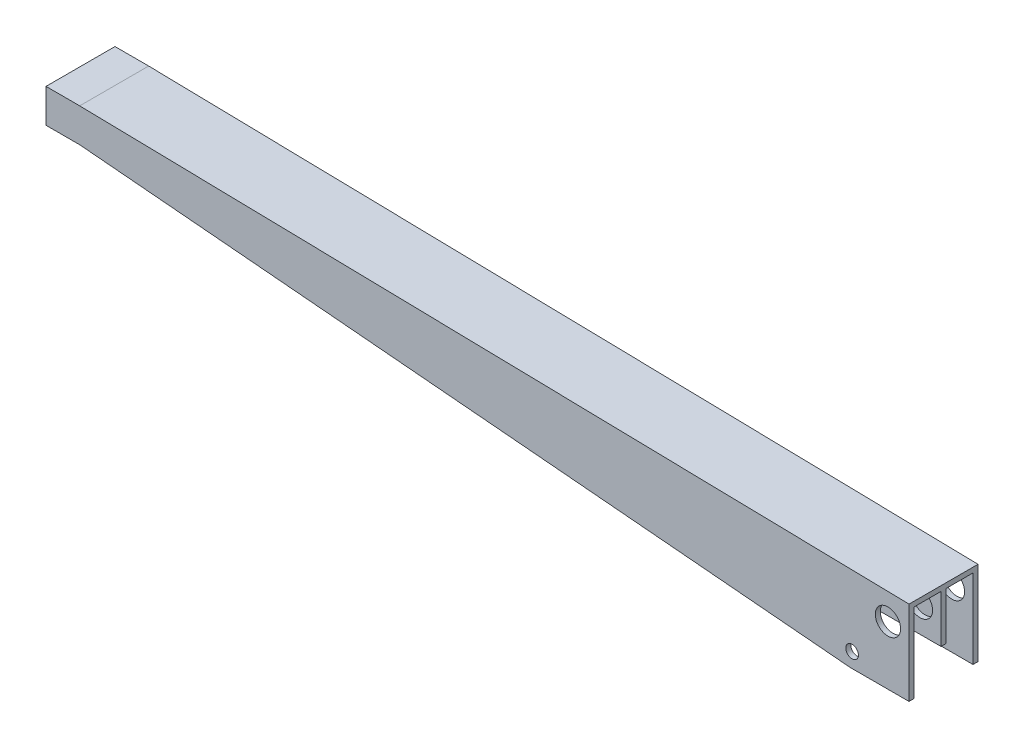
SolidWorks part; units mm, degrees
material "AISI 1045 Steel, cold drawn"
ref_plane "Front Plane" through (0, 0, 0) normal (0, 0, 1) x (1, 0, 0)
ref_plane "Top Plane" through (0, 0, 0) normal (0, 1, 0) x (1, 0, 0)
ref_plane "Right Plane" through (0, 0, 0) normal (1, 0, 0) x (0, 0, -1)
sketch "Sketch1" plane through (0, 0, 0) normal (0, 0, 1) x (1, 0, 0)
  line L0 (-2600, 304.8) -> (-2498.4, 304.8)
  line L1 (-2600, 304.8) -> (-2600, 203.2)
  line L2 (-2600, 203.2) -> (-2498.4, 203.2)
  line L4 (-177.8, 0) -> (0, 0)
  line L5 (0, 0) -> (0, 254)
  line L6 (0, 254) -> (-2498.4, 304.8)
  line L7 (-2498.4, 203.2) -> (-177.8, 0)
  dimension "D1" = 101.6
  dimension "D2" = 101.6
  dimension "D3" = 2600
  dimension "D4" = 177.8
  dimension "D6" = 203.2
  dimension "D7" = 254
extrude "Boss-Extrude1" add sketch "Sketch1" against normal blind 15
ref_plane "Plane1" through (0, 0, 177.8) normal (0, 0, 1) x (1, 0, 0)
sketch "Sketch2" plane through (0, 0, 177.8) normal (0, 0, 1) x (1, 0, 0)
  line L8 (-2498.4, 203.2) -> (-177.8, 0)
  line L10 (-177.8, 0) -> (0, 0)
  line L11 (0, 0) -> (0, 254)
  line L12 (0, 254) -> (-2498.4, 304.8)
  line L13 (-2498.4, 304.8) -> (-2600, 304.8)
  line L14 (-2600, 304.8) -> (-2600, 203.2)
  line L15 (-2600, 203.2) -> (-2498.4, 203.2)
  line L16 (-2498.4, 203.2) -> (-177.8, 0)
  line L18 (-177.8, 0) -> (0, 0)
  line L19 (0, 0) -> (0, 254)
  line L20 (0, 254) -> (-2498.4, 304.8)
  line L21 (-2498.4, 304.8) -> (-2600, 304.8)
  line L22 (-2600, 304.8) -> (-2600, 203.2)
  line L23 (-2600, 203.2) -> (-2498.4, 203.2)
  dimension "D1" = 0
extrude "Boss-Extrude2" add sketch "Sketch2" along normal blind 15 separate body
sketch "Sketch3" plane through (0, 0, 192.8) normal (0, 0, 1) x (1, 0, 0)
  line L6 (-2600, 289.8) -> (-2600, 304.8)
  line L7 (-2600, 304.8) -> (-2498.4, 304.8)
  line L8 (-2498.4, 304.8) -> (0, 254)
  line L9 (-15, 0) -> (-15, 239.3019)
  line L10 (-15, 239.3019) -> (-2498.5525, 289.8)
  line L11 (-2498.5525, 289.8) -> (-2600, 289.8)
  line L12 (-15, 239.3019) -> (0, 238.9969)
  line L13 (-15, 239.3019) -> (-2498.5525, 289.8)
  line L14 (-2498.5525, 289.8) -> (-2600, 289.8)
  line L15 (0, 0) -> (0, 254) construction
  line L16 (0, 238.9969) -> (0, 254)
  dimension "D1" = 15
extrude "Boss-Extrude3" add sketch "Sketch3" against normal up to surface (192.8 mm away) up to face at (-1482.0857, 181.4286, 0)
ref_plane "Plane2" through (0, 0, 88.9) normal (0, 0, 1) x (1, 0, 0)
sketch "Sketch6" plane through (0, 0, 88.9) normal (0, 0, 1) x (1, 0, 0)
  line L8 (-2498.4, 203.2) -> (-177.8, 0)
  line L10 (-177.8, 0) -> (0, 0)
  line L11 (0, 0) -> (0, 254)
  line L12 (0, 254) -> (-2498.4, 304.8)
  line L13 (-2498.4, 304.8) -> (-2600, 304.8)
  line L14 (-2600, 304.8) -> (-2600, 203.2)
  line L15 (-2600, 203.2) -> (-2498.4, 203.2)
  line L16 (-2498.4, 203.2) -> (-177.8, 0)
  line L18 (-177.8, 0) -> (0, 0)
  line L19 (0, 0) -> (0, 254)
  line L20 (0, 254) -> (-2498.4, 304.8)
  line L21 (-2498.4, 304.8) -> (-2600, 304.8)
  line L22 (-2600, 304.8) -> (-2600, 203.2)
  line L23 (-2600, 203.2) -> (-2498.4, 203.2)
  dimension "D1" = 0
extrude "Boss-Extrude4" add sketch "Sketch6" along normal blind 7.5 and the other way blind 7.5
sketch "Sketch5" plane through (0, 0, 192.8) normal (0, 0, 1) x (1, 0, 0)
  line L1 (0, 238.9969) -> (-2498.5525, 289.8) construction
  line L2 (-177.8, 0) -> (0, 0) construction
  line L3 (0, 0) -> (0, 254) construction
  circle A0 centre (-63.5, 176.7828) radius 38.1
  circle A1 centre (-171.45, 44.45) radius 19.05
  point P2 (-25.4, 176.7828)
  point P5 (-63.5, 214.8828)
  point P9 (-171.45, 25.4)
  point P10 (-190.5, 44.45)
  point P13 (-101.6, 176.7828)
  point P21 (-152.4, 44.45)
  dimension "D1" = 25.4
  dimension "D3" = 76.2
  dimension "D6" = 38.1
  dimension "D2" = 25.4
  dimension "D4" = 25.4
  dimension "D5" = 50.8
extrude "Cut-Extrude1" cut sketch "Sketch5" against normal through all
sketch "Sketch7" plane through (0, 0, 96.4) normal (0, 0, 1) x (1, 0, 0)
  line L0 (-1265.5813, 95.25) -> (0, 95.25)
  line L1 (0, 95.25) -> (0, 0)
  line L2 (0, 0) -> (-177.8, 0)
  line L3 (-177.8, 0) -> (0, 0) construction
  line L4 (0, 0) -> (0, 238.9969) construction
  line L5 (-2498.4, 203.2) -> (-177.8, 0) construction
  line L6 (-1265.5813, 95.25) -> (-177.8, 0)
  dimension "D1" = 95.25
extrude "Cut-Extrude2" cut sketch "Sketch7" against normal up to surface (15 mm away) up to face at (-152.4, 44.45, 81.4)
sketch "Sketch8" plane through (0, 304.8, 0) normal (0, 1, 0) x (1, 0, 0)
  line L0 (-2600, -88.9) -> (-2498.4, -88.9) construction
  line L1 (-2600, 15) -> (-2600, -192.8) construction
  line L2 (-2498.4, 15) -> (-2498.4, -192.8) construction
  line L3 (-2549.2, 15) -> (-2549.2, -192.8) construction
  line L4 (-2498.4, 15) -> (-2600, 15) construction
  line L5 (-2498.4, -192.8) -> (-2600, -192.8) construction
  circle A0 centre (-2549.2, -88.9) radius 25.4
  dimension "D1" = 50.8
